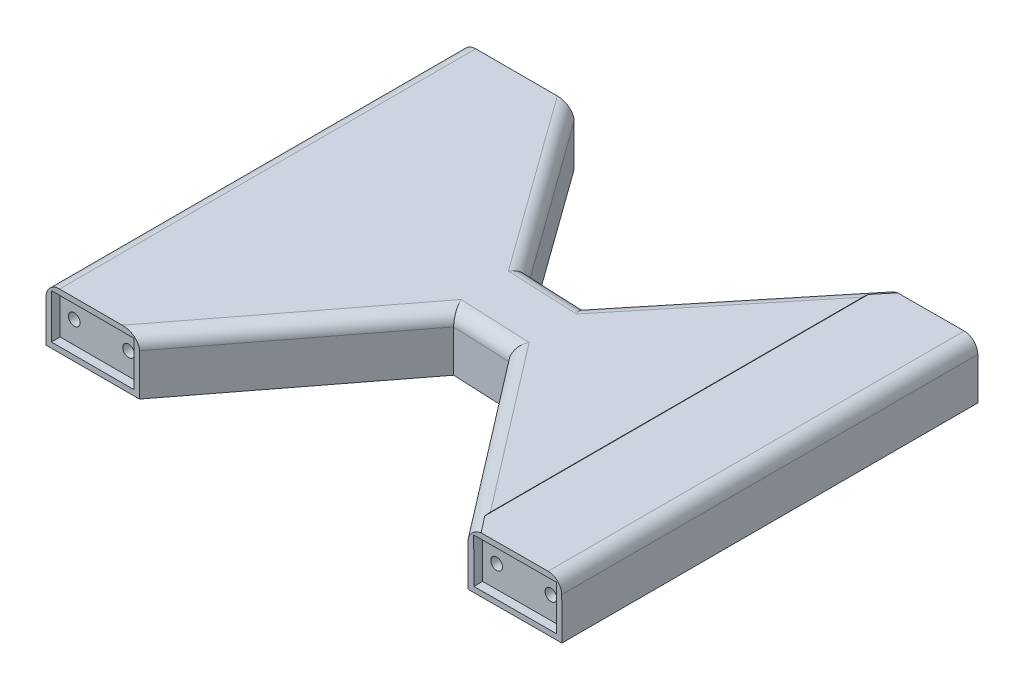
SolidWorks part; units mm, degrees
ref_plane "Front Plane" through (0, 0, 0) normal (0, 0, 1) x (1, 0, 0)
ref_plane "Top Plane" through (0, 0, 0) normal (0, 1, 0) x (1, 0, 0)
ref_plane "Right Plane" through (0, 0, 0) normal (1, 0, 0) x (0, 0, -1)
sketch "Sketch1" plane through (0, 0, 0) normal (0, 0, 1) x (1, 0, 0)
  line L12 (-28.3329, -0.106) -> (2.0671, -0.106)
  line L13 (-28.3329, 16.294) -> (-28.3329, -0.106)
  line L14 (2.0671, 16.294) -> (-28.3329, 16.294)
  line L15 (2.0671, -0.106) -> (2.0671, 16.294)
  line L16 (-30.3329, 18.294) -> (-30.3329, -2.106)
  line L17 (-30.3329, -2.106) -> (4.0671, -2.106)
  line L18 (4.0671, -2.106) -> (4.0671, 18.294)
  line L19 (4.0671, 18.294) -> (-30.3329, 18.294)
  line L24 (127.2095, -0.2643) -> (157.6092, -0.1355)
  line L25 (157.6092, -0.1355) -> (157.5398, 16.2643)
  line L26 (127.14, 16.1356) -> (127.2095, -0.2643)
  line L27 (157.5398, 16.2643) -> (127.14, 16.1356)
  line L28 (125.218, -2.2727) -> (159.6177, -2.127)
  line L29 (159.6177, -2.127) -> (159.5313, 18.2728)
  line L30 (159.5313, 18.2728) -> (125.1316, 18.1271)
  line L31 (125.1316, 18.1271) -> (125.218, -2.2727)
  dimension "D3" = 2
extrude "Boss-Extrude1" add sketch "Sketch1" along normal blind 3.2
sketch "Sketch2" plane through (0, 0, 3) normal (0, 0, 1) x (1, 0, 0)
  circle A2 centre (-23.1329, 8.094) radius 2.15
  circle A3 centre (-3.1329, 8.094) radius 2.15
  circle A6 centre (132.3747, 7.9577) radius 2.15
  circle A7 centre (152.3745, 8.0424) radius 2.15
  dimension "D1" = 4.3
  dimension "D2" = 132.3747
  dimension "D3" = 152.3745
  dimension "D4" = 3.1329
  dimension "D5" = 23.1329
  dimension "D6" = 7.9577
  dimension "D7" = 8.0424
  dimension "D8" = 8.094
sketch "Sketch4" plane through (0, 0, 3.2) normal (0, 0, 1) x (1, 0, 0)
  line L4 (4.0671, 18.294) -> (-30.3329, 18.294)
  line L5 (-30.3329, 18.294) -> (-30.3329, -2.106)
  line L6 (-30.3329, -2.106) -> (4.0671, -2.106)
  line L7 (4.0671, -2.106) -> (4.0671, 18.294)
  line L8 (4.0671, 18.294) -> (-30.3329, 18.294)
  line L9 (-30.3329, 18.294) -> (-30.3329, -2.106)
  line L10 (-30.3329, -2.106) -> (4.0671, -2.106)
  line L11 (4.0671, -2.106) -> (4.0671, 18.294)
  line L12 (125.1316, 18.1271) -> (125.218, -2.2727)
  line L13 (125.218, -2.2727) -> (159.6177, -2.127)
  line L14 (159.6177, -2.127) -> (159.5313, 18.2728)
  line L15 (159.5313, 18.2728) -> (125.1316, 18.1271)
  line L16 (125.1316, 18.1271) -> (125.218, -2.2727)
  line L17 (125.218, -2.2727) -> (159.6177, -2.127)
  line L18 (159.6177, -2.127) -> (159.5313, 18.2728)
  line L19 (159.5313, 18.2728) -> (125.1316, 18.1271)
  dimension "D1" = 0
  dimension "D2" = 0
extrude "Boss-Extrude2" add sketch "Sketch4" along normal blind 150
sketch "Sketch5" plane through (0, 0, 153.2) normal (0, 0, 1) x (1, 0, 0)
  line L8 (2.0671, -0.106) -> (2.0671, 16.294)
  line L9 (2.0671, 16.294) -> (-28.3329, 16.294)
  line L10 (-28.3329, 16.294) -> (-28.3329, -0.106)
  line L11 (-28.3329, -0.106) -> (2.0671, -0.106)
  line L12 (2.0671, -0.106) -> (2.0671, 16.294)
  line L13 (2.0671, 16.294) -> (-28.3329, 16.294)
  line L14 (-28.3329, 16.294) -> (-28.3329, -0.106)
  line L15 (-28.3329, -0.106) -> (2.0671, -0.106)
  line L20 (157.5398, 16.2643) -> (127.14, 16.1356)
  line L21 (127.14, 16.1356) -> (127.2095, -0.2643)
  line L22 (127.2095, -0.2643) -> (157.6092, -0.1355)
  line L23 (157.6092, -0.1355) -> (157.5398, 16.2643)
  line L24 (157.5398, 16.2643) -> (127.14, 16.1356)
  line L25 (127.14, 16.1356) -> (127.2095, -0.2643)
  line L26 (127.2095, -0.2643) -> (157.6092, -0.1355)
  line L27 (157.6092, -0.1355) -> (157.5398, 16.2643)
  dimension "D3" = 30.4
  dimension "D4" = 16.4
  dimension "D1" = 2
  dimension "D2" = 2
extrude "Cut-Extrude2" cut sketch "Sketch5" against normal blind 3.2
sketch "Sketch12" plane through (0, 18.294, 0) normal (0, 1, 0) x (1, 0, 0)
  line L0 (4.0671, -153.2) -> (125.0967, -153.2) construction
  point P3 (64.5819, -153.2)
sketch "Sketch13" plane through (4.0671, 0, 0) normal (1, 0, 0) x (0, 0, -1)
  line L4 (0, -2.106) -> (0, 18.294)
  line L5 (0, 18.294) -> (-153.2, 18.294)
  line L6 (-153.2, 18.294) -> (-153.2, -2.106)
  line L7 (-153.2, -2.106) -> (0, -2.106)
  line L8 (0, -2.106) -> (0, 18.294)
  line L9 (0, 18.294) -> (-153.2, 18.294)
  line L10 (-153.2, 18.294) -> (-153.2, -2.106)
  line L11 (-153.2, -2.106) -> (0, -2.106)
  dimension "D1" = 0
extrude "Boss-Extrude4" add sketch "Sketch13" along normal up to surface (121.0637 mm away) up to face at (125.1748, 7.9272, 76.6)
sketch "Sketch14" plane through (0, 18.294, 0) normal (0, 1, 0) x (1, 0, 0)
  line L0 (64.5819, -153.2) -> (64.5819, 0) construction
  line L1 (125.1309, 0) -> (-30.3329, 0) construction
  line L2 (4.0671, -153.2) -> (64.5819, -74.3356)
  line L3 (64.5819, -74.3356) -> (125.0967, -153.2)
  line L4 (64.5819, -74.3356) -> (125.1309, 0)
  line L5 (64.5819, -74.3356) -> (10.8984, 0)
  line L6 (54.2916, -87.7462) -> (75.5913, -88.6834)
  line L7 (54.2134, -59.9783) -> (75.5131, -60.9155)
  line L8 (75.5131, -60.9155) -> (75.5913, -88.6834)
  line L9 (54.2134, -59.9783) -> (54.2916, -87.7462)
  point P5 (64.5819, -74.3356)
  line M7 (125.1309, 0) -> (-30.3329, 0)
  line M9 (-30.3329, -153.2) -> (125.1309, -153.2)
  dimension "D1" = 75
  dimension "D2" = 75
extrude "Cut-Extrude3" cut sketch "Sketch14" against normal up to surface (20.4 mm away) contours L0 L6 L2 M9 | L0 L3 L6 M9 | L0 L7 L4 M7 | L7 L0 L5 M7 region at (43.8945, 18.294, 128.2518) region at (85.2987, 18.294, 128.3382) region at (46.1464, 18.294, 23.2745) region at (85.3428, 18.294, 23.3652) up to face at (8.5547, -2.106, 95.75)
fillet "Fillet1" radius 5 8 edges at (100.344, 18.294, 120.9417) (64.9415, 18.294, 88.2148) (29.1794, 18.294, 120.4731) (100.322, 18.294, 30.4577) (64.8632, 18.294, 60.4469) (32.5559, 18.294, 29.9892) (159.5313, 18.2728, 76.6) (-30.3329, 18.294, 76.6)
extrude "Cut-Extrude5" cut sketch "Sketch2" along normal up to surface (147 mm away) up to face at (142.3746, 8, 150)
